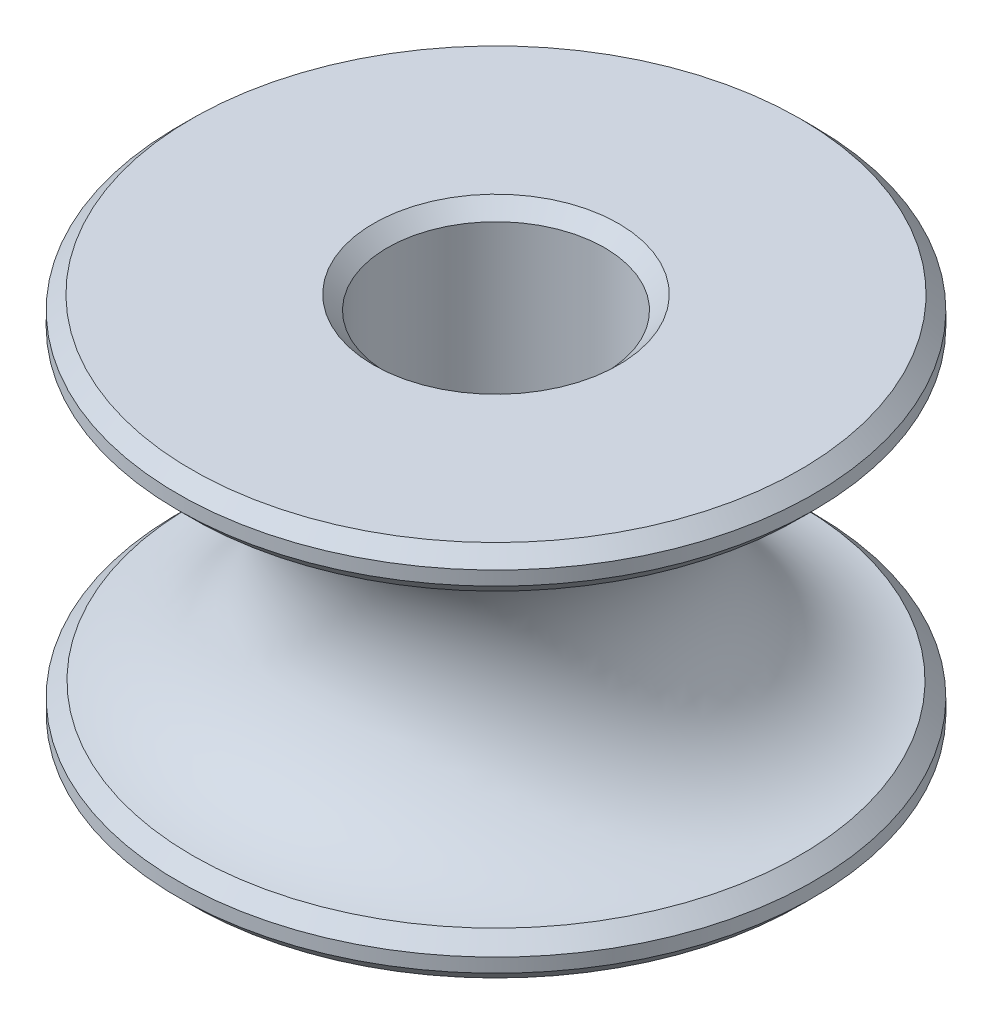
SolidWorks part; units mm, degrees
ref_plane "Front Plane" through (0, 0, 0) normal (0, 0, 1) x (1, 0, 0)
ref_plane "Top Plane" through (0, 0, 0) normal (0, 1, 0) x (1, 0, 0)
ref_plane "Right Plane" through (0, 0, 0) normal (1, 0, 0) x (0, 0, -1)
sketch "Sketch1" plane through (0, 0, 0) normal (1, 0, 0) x (0, 0, -1)
  line L0 (7.775, 27) -> (22.775, 27)
  line L1 (0, 0) -> (7.775, 0) construction
  line L2 (0, 0) -> (0, 27) construction
  line L3 (0, 27) -> (7.775, 27) construction
  line L4 (7.775, 0) -> (7.775, 27) construction
  line L5 (22.775, 27) -> (22.775, 24)
  line L6 (7.775, 0) -> (22.775, 0)
  line L7 (22.775, 0) -> (22.775, 3)
  line L8 (7.775, 13.5) -> (22.775, 13.5) construction
  line L9 (22.775, 27) -> (22.775, 0) construction
  line L10 (7.775, 27) -> (7.775, 0)
  arc A0 (22.775, 24) -> (22.775, 3) centre (22.775, 13.5) ccw
  dimension "D1" = 27
  dimension "D2" = 7.775
  dimension "D3" = 3
  dimension "D4" = 15
revolve "Revolve1" add sketch "Sketch1" angle 360 about L2 region at (0, 26.6911, -15.275)
chamfer "Chamfer1" distance 1 angle 45 6 edges at (0, 27, -7.775) (0, 0, -7.775) (0, 0, -22.775) (0, 3, -22.775) (0, 24, -22.775) (0, 27, -22.775)
